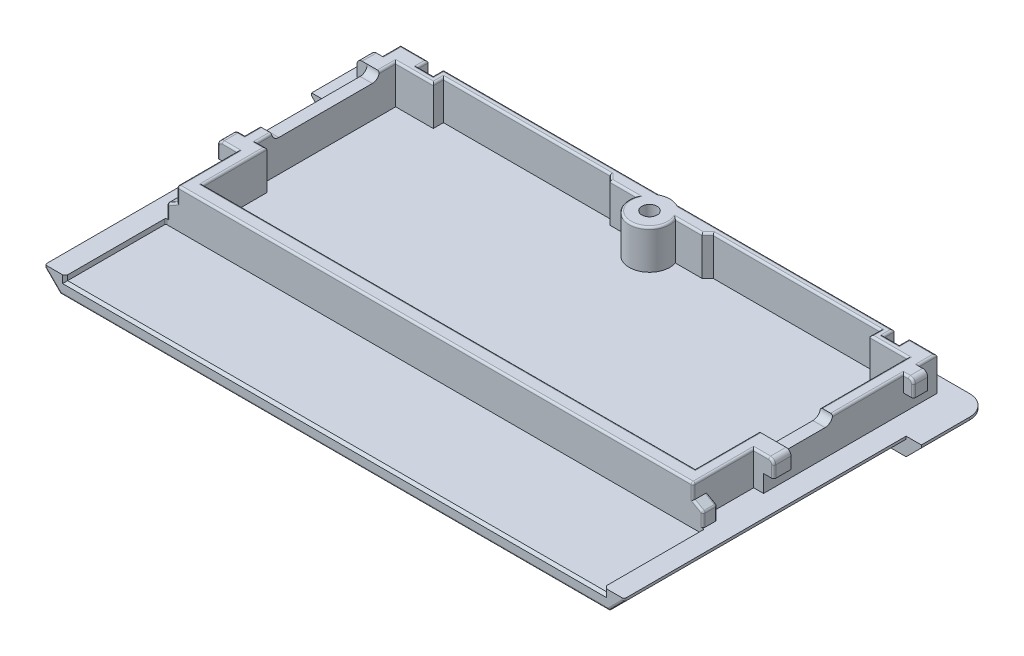
SolidWorks part; units mm, degrees
ref_plane "Front Plane" through (0, 0, 0) normal (0, 0, 1) x (1, 0, 0)
ref_plane "Top Plane" through (0, 0, 0) normal (0, 1, 0) x (1, 0, 0)
ref_plane "Right Plane" through (0, 0, 0) normal (1, 0, 0) x (0, 0, -1)
sketch "Sketch1" plane through (0, 0, 0) normal (0, 1, 0) x (1, 0, 0)
  line L0 (0, -17.25) -> (0, 17.25) construction
  line L1 (28, 17.25) -> (0, 17.25)
  line L2 (30, 15.25) -> (30, 10.5)
  line L3 (28.5, -17.25) -> (0, -17.25)
  line L5 (0, 17.25) -> (0, -17.25)
  line L6 (0, 17.25) -> (0, 21.7445) construction
  line L14 (30, 10.5) -> (28.5, 10.5)
  line L15 (28.5, -17.25) -> (28.5, 10.5)
  arc A0 (28, 17.25) -> (30, 15.25) centre (28, 15.25) cw
  point P0 (0, 0)
  point P2 (0, 0)
  dimension "D3" = 2
  dimension "D1" = 60
  dimension "D2" = 34.5
  dimension "D4" = 27.75
  dimension "D5" = 57
extrude "Boss-Extrude1" add sketch "Sketch1" along normal blind 5.1
sketch "Sketch22" plane through (0, 5.1, 0) normal (0, 1, 0) x (1, 0, 0)
  line L0 (28, 17.25) -> (0, 17.25) construction
  line L3 (0, -5.95) -> (24.2, -5.95)
  line L5 (4.525, 14.4) -> (5.075, 14.95)
  line L7 (22.175, 15.65) -> (22.175, 14.65)
  line L8 (22.175, 14.65) -> (23.675, 14.65)
  line L9 (23.675, 15.65) -> (23.675, 14.65)
  line L12 (1.8914, 14.4) -> (4.525, 14.4)
  line L14 (26.375, 13.75) -> (27.375, 13.75)
  line L16 (26.375, 12.35) -> (27.375, 12.35)
  line L17 (27.375, 13.75) -> (27.375, 12.35)
  line L22 (5.075, 14.95) -> (21.475, 14.95)
  line L23 (0.6245, 15.65) -> (22.175, 15.65)
  line L24 (0, 17.25) -> (0, -17.25) construction
  line L25 (26.375, 15.65) -> (26.375, 13.75)
  line L26 (25.175, 0.3) -> (25.175, 13.95)
  line L27 (28.5, -17.25) -> (28.5, 10.5) construction
  line L29 (26.375, -5.95) -> (26.375, -7.35)
  line L30 (26.375, -7.35) -> (0, -7.35)
  line L32 (28.5, 10.5) -> (30, 10.5) construction
  line L33 (21.475, 13.95) -> (25.175, 13.95)
  line L34 (0, -17.25) -> (28.5, -17.25) construction
  line L35 (30, 10.5) -> (30, 15.25) construction
  line L36 (26.375, -5.95) -> (25.4, -5.95)
  line L37 (0, -17.25) -> (28.5, -17.25)
  line L38 (28.5, -17.25) -> (28.5, 10.5)
  line L39 (21.475, 14.95) -> (21.475, 13.95)
  line L40 (28.5, 10.5) -> (30, 10.5)
  line L41 (26.375, 12.35) -> (27.375, 12.35)
  line L42 (21.475, 15.65) -> (21.475, 13.95) construction
  line L43 (30, 10.5) -> (30, 15.25)
  line L44 (23.675, 15.65) -> (26.375, 15.65)
  line L45 (24.375, 15.65) -> (24.375, 13.95) construction
  line L46 (21.475, 13.95) -> (24.375, 13.95) construction
  line L47 (28, 17.25) -> (0, 17.25)
  line L49 (0, 17.25) -> (0, -5.95)
  line L50 (0, -7.35) -> (0, -17.25)
  line L51 (25.4, -5.95) -> (25.4, -1.4)
  line L52 (25.4, -1.4) -> (27.375, -1.4)
  line L53 (27.375, -1.4) -> (27.375, 0.3)
  line L54 (27.375, 0.3) -> (26.375, 0.3)
  line L55 (26.375, 0.3) -> (26.375, 12.35)
  line L56 (24.2, -5.95) -> (24.2, 0.3)
  line L57 (24.2, 0.3) -> (25.175, 0.3)
  line L58 (25.4, -5.95) -> (26.375, -5.95)
  line L59 (24.2, -5.95) -> (0, -5.95)
  line L60 (0, -17.25) -> (0, -22.9738) construction
  arc A0 (30, 15.25) -> (28, 17.25) centre (28, 15.25) ccw construction
  arc A1 (30, 15.25) -> (28, 17.25) centre (28, 15.25) ccw
  arc A2 (0, 11.75) -> (1.8914, 14.4) centre (0, 13.75) ccw
  arc A3 (0.6245, 15.65) -> (0, 15.75) centre (0, 13.75) ccw
  arc M26 (30, 15.25) -> (28, 17.25) centre (28, 15.25) ccw
  line M27 (28, 17.25) -> (0, 17.25)
  line M28 (0, 17.25) -> (0, -17.25)
  line M29 (0, -17.25) -> (28.5, -17.25)
  line M30 (28.5, -17.25) -> (28.5, 10.5)
  line M31 (28.5, 10.5) -> (30, 10.5)
  line M32 (30, 10.5) -> (30, 15.25)
  dimension "D23" = 4
  dimension "D2" = 1.5
  dimension "D3" = 2.7
  dimension "D4" = 1.2
  dimension "D5" = 34.5
  dimension "D6" = 12.05
  dimension "D7" = 3.5
  dimension "D8" = 1.6
  dimension "D9" = 1.25
  dimension "D10" = 0.7
  dimension "D11" = 45
  dimension "D12" = 21.3
  dimension "D13" = 1
  dimension "D14" = 1.4
  dimension "D15" = 23
  dimension "D16" = 52.75
  dimension "D17" = 54.75
  dimension "D18" = 1.4
  dimension "D19" = 1.7
  dimension "D20" = 1.2
  dimension "D21" = 1.5
  dimension "D22" = 50.8
  dimension "D1" = 0.7
extrude "Cut-Extrude17" cut sketch "Sketch22" against normal blind 3.34 contours L9 L44 L25 L14 L17 L16 L26 L33 L39 L22 L5 L12 L3 L29 L30 L23 L7 L8 M28 M29 M30 M31 M32 M26 M27 | L56 L57 L26 L33 L39 L22 L5 L12 L3 M28
sketch "Sketch23" plane through (0, 1.76, 0) normal (0, 1, 0) x (1, 0, 0)
  line L0 (0, -17.25) -> (28.5, -17.25) construction
  line L1 (0, -7.35) -> (26.375, -7.35)
  line L2 (0, -7.35) -> (0, -17.25)
  line L3 (0, -17.25) -> (26.5, -17.25)
  line L4 (26.5, -7.475) -> (26.5, -17.25)
  line L5 (0, -17.25) -> (0, -26.2479) construction
  arc A0 (26.375, -7.35) -> (26.5, -7.475) centre (26.375, -7.475) cw
  dimension "D1" = 53
extrude "Cut-Extrude18" cut sketch "Sketch23" against normal blind 0.5
sketch "Sketch25" plane through (0, 1.76, 0) normal (0, 1, 0) x (1, 0, 0)
  line L10 (0, 11.75) -> (0, -5.95)
  line L11 (0, 11.75) -> (0, -5.95)
  line L16 (24.2, -5.95) -> (24.2, 0.3)
  line L17 (24.2, 0.3) -> (25.175, 0.3)
  line L18 (25.175, 0.3) -> (25.175, 13.95)
  line L19 (25.175, 13.95) -> (21.475, 13.95)
  line L20 (21.475, 13.95) -> (21.475, 14.95)
  line L21 (21.475, 14.95) -> (5.075, 14.95)
  line L22 (5.075, 14.95) -> (4.525, 14.4)
  line L23 (4.525, 14.4) -> (1.8914, 14.4)
  line L31 (0, -5.95) -> (24.2, -5.95)
  line L32 (24.2, -5.95) -> (24.2, 0.3)
  line L33 (24.2, 0.3) -> (25.175, 0.3)
  line L34 (25.175, 0.3) -> (25.175, 13.95)
  line L35 (25.175, 13.95) -> (21.475, 13.95)
  line L36 (21.475, 13.95) -> (21.475, 14.95)
  line L37 (21.475, 14.95) -> (5.075, 14.95)
  line L38 (5.075, 14.95) -> (4.525, 14.4)
  line L39 (4.525, 14.4) -> (1.8914, 14.4)
  line L47 (0, -5.95) -> (24.2, -5.95)
  arc A1 (0, 11.75) -> (1.8914, 14.4) centre (0, 13.75) ccw
  arc A2 (0, 11.75) -> (1.8914, 14.4) centre (0, 13.75) ccw
  dimension "D1" = 0
extrude "Cut-Extrude19" cut sketch "Sketch25" against normal blind 0.5
sketch "Sketch34" plane through (0, 0, 1.4) normal (0, 0, 1) x (1, 0, 0)
  line L1 (27.375, 1.76) -> (26.375, 1.76)
  line L2 (27.375, 1.76) -> (27.375, 3.46)
  line L3 (27.375, 3.46) -> (26.375, 3.46)
  line L4 (26.375, 1.76) -> (26.375, 3.46)
  line L5 (26.375, 1.76) -> (26.375, 5.1) construction
  dimension "D1" = 1.7
extrude "Cut-Extrude25" cut sketch "Sketch34" against normal through all
sketch "Sketch35" plane through (0, 0, 7.35) normal (0, 0, 1) x (1, 0, 0)
  line L0 (25.4, 5.1) -> (25.4, 3.65)
  line L1 (26.375, 5.1) -> (0, 5.1) construction
  line L2 (25.4, 3.65) -> (26.375, 3.0871)
  line L3 (26.375, 1.76) -> (26.375, 5.1) construction
  line L4 (26.375, 3.0871) -> (26.375, 5.1)
  line L5 (26.375, 5.1) -> (25.4, 5.1)
  line L6 (25.4, 1.76) -> (25.4, 5.1) construction
  dimension "D1" = 30
  dimension "D2" = 1.45
extrude "Cut-Extrude26" cut sketch "Sketch35" against normal up to surface (1.4 mm away) up to face at (25.8875, 3.43, 5.95)
mirror "Mirror10" about plane through (0, 0, 0) normal (1, 0, 0) of "Cut-Extrude26", "Cut-Extrude25", "Boss-Extrude1", "Cut-Extrude17", "Cut-Extrude18", "Cut-Extrude19"
sketch "Sketch36" plane through (26.375, 0, 0) normal (1, 0, 0) x (0, 0, -1)
  line L0 (0.3, 5.1) -> (12.35, 5.1) construction
  line L1 (0.3, 3.46) -> (0.3, 5.1) construction
  line L2 (1.05, 4.35) -> (4.65, 4.35)
  line L3 (1.05, 5.85) -> (4.65, 5.85)
  arc A0 (4.65, 4.35) -> (4.65, 5.85) centre (4.65, 5.1) ccw
  arc A1 (1.05, 5.85) -> (1.05, 4.35) centre (1.05, 5.1) ccw
  dimension "D1" = 0.75
  dimension "D2" = 5.1
extrude "Cut-Extrude27" cut sketch "Sketch36" against normal up to surface (1.2 mm away) up to face at (25.175, 3.18, -7.125)
sketch "Sketch37" plane through (-26.375, 0, 0) normal (-1, 0, 0) x (0, 0, 1)
  line L0 (-11.65, 5.1) -> (-2.45, 5.1) construction
  line L1 (-0.3, 5.1) -> (-12.35, 5.1) construction
  line L2 (-11.65, 5.8) -> (-2.45, 5.8)
  line L3 (-11.65, 4.4) -> (-2.45, 4.4)
  line L4 (-12.35, 3.46) -> (-12.35, 5.1) construction
  arc A0 (-11.65, 5.8) -> (-11.65, 4.4) centre (-11.65, 5.1) ccw
  arc A1 (-2.45, 4.4) -> (-2.45, 5.8) centre (-2.45, 5.1) ccw
  point P4 (-7.05, 5.1)
  dimension "D1" = 10.6
  dimension "D2" = 0.7
extrude "Cut-Extrude28" cut sketch "Sketch37" against normal up to surface (1.2 mm away) up to face at (-25.175, 3.18, -7.125)
sketch "Sketch33" plane through (0, 5.1, 0) normal (0, 1, 0) x (1, 0, 0)
  circle A0 centre (0, 13.75) radius 0.75
  arc A1 (-1.8914, 14.4) -> (1.8914, 14.4) centre (0, 13.75) ccw construction
  dimension "D1" = 1.5
extrude "Cut-Extrude24" cut sketch "Sketch33" against normal offset from surface (4.6 mm away) 0.5 up to face at (0, 0, -7.3328)
chamfer "Chamfer6" distance 1.5 angle 45 5 edges at (29.4142, 0, -16.6642) (-29.4142, 0, -16.6642) (-30, 0, -12.875) (30, 0, -12.875) (0, 0, -17.25)
fillet "Fillet2" radius 0.2 17 edges at (25.4, 4.375, 7.35) (25.8875, 3.3685, 7.35) (25.8875, 3.3685, 5.95) (26.375, 3.0871, 6.65) (-28.5, 1.63, 17.25) (-26.375, 2.4235, 5.95) (-26.375, 2.4235, 7.35) (28.5, 1.63, 17.25) (-25.4, 4.375, 7.35) (-25.8875, 3.3685, 7.35) (-26.375, 3.0871, 6.65) (-25.8875, 3.3685, 5.95) (0, 0, 17.25) (27.75, 0.75, 17.25) (-27.75, 0.75, 17.25) (26.375, 2.4235, 7.35) (26.375, 2.4235, 5.95)
fillet "Fillet3" radius 0.5 4 edges at (-27.375, 5.1, -13.05) (-27.375, 5.1, 0.55) (27.375, 5.1, 0.55) (27.375, 5.1, -13.05)
fillet "Fillet5" radius 0.2 45 edges at (27.375, 4.03, -12.35) (27.375, 4.03, 1.4) (-24.2, 5.1, 2.825) (-25.175, 5.1, -1.025) (-3.2082, 5.1, -14.4) (-4.8, 5.1, -14.675) (-13.275, 5.1, -14.95) (-21.475, 5.1, -14.45) (-23.325, 5.1, -13.95) (-11.3997, 5.1, -15.65) (-22.175, 5.1, -15.15) (-22.925, 5.1, -14.65) (-25.025, 5.1, -15.65) (-26.375, 5.1, -14.7) (-26.1375, 5.1, 1.4) (-26.375, 5.1, -1.025) (-23.675, 5.1, -15.15) (-27.375, 4.03, 1.4) (-27.375, 4.03, -0.3) (3.2082, 5.1, -14.4) (4.8, 5.1, -14.675) (25.175, 5.1, -9.675) (26.375, 5.1, -8.875) (13.275, 5.1, -14.95) (21.475, 5.1, -14.45) (23.325, 5.1, -13.95) (-25.175, 5.1, -13.15) (0, 5.1, 5.95) (24.2, 5.1, 2.825) (0, 5.1, 7.35) (-25.4, 5.1, 4.275) (25.4, 5.1, 4.275) (25.3414, 5.1, 7.2914) (-25.3414, 5.1, 7.2914) (-27.2286, 4.9536, -0.3) (-27.2286, 4.9536, 1.4) (27.2286, 4.9536, -12.35) (27.2286, 4.9536, 1.4) (26.1375, 5.1, 1.4) (23.675, 5.1, -15.15) (11.3997, 5.1, -15.65) (22.175, 5.1, -15.15) (22.925, 5.1, -14.65) (25.025, 5.1, -15.65) (26.375, 5.1, -14.7)
chamfer "Chamfer3" distance 0.25 angle 45 3 edges at (0, 1.26, 17.25) (26.5, 1.51, 17.25) (-26.5, 1.51, 17.25)
sketch "Sketch38" plane through (0, 0, 0) normal (0, -1, 0) x (1, 0, 0)
  line L0 (0, 0) -> (0, -17.25) construction
  line L1 (28, -17.25) -> (-28, -17.25) construction
  line L2 (22.6039, -11.5) -> (-22.6039, -11.5)
  line L3 (28.5, -10.5) -> (27, -10.5) construction
  arc A0 (-22.6039, -11.5) -> (22.6039, -11.5) centre (0, 54.75) ccw
  point P10 (0, -11.5)
  dimension "D3" = 70
  dimension "D1" = 2
  dimension "D2" = 1
extrude "Cut-Extrude29" cut sketch "Sketch38" against normal offset from surface (0.26 mm away) 1 up to face at (0, 1.26, -8.8806)
chamfer "Chamfer7" distance 1 angle 45 2 edges at (0, 0.26, -11.5) (0, 0.26, -15.25)
